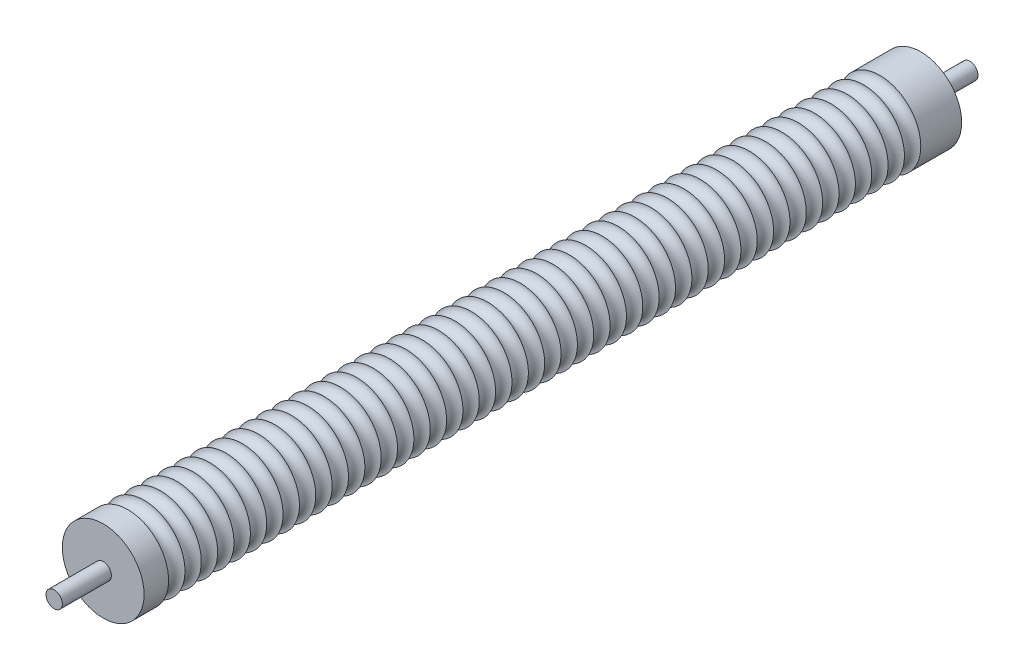
SolidWorks part; units mm, degrees
ref_plane "Front Plane" through (0, 0, 0) normal (0, 0, 1) x (1, 0, 0)
ref_plane "Top Plane" through (0, 0, 0) normal (0, 1, 0) x (1, 0, 0)
ref_plane "Right Plane" through (0, 0, 0) normal (1, 0, 0) x (0, 0, -1)
sketch "Sketch1" plane through (0, 0, 0) normal (0, 0, 1) x (1, 0, 0)
  circle A0 centre (0, 0) radius 50
  dimension "D1" = 100
extrude "Boss-Extrude1" add sketch "Sketch1" along normal blind 1000
sketch "Sketch2" plane through (0, 0, 0) normal (0, 1, 0) x (1, 0, 0)
  line L0 (-50, 0) -> (-50, -1000) construction
  line L1 (-50, -1000) -> (50, -1000) construction
  line L2 (0, 0) -> (0, -1000) construction
  line L3 (-50, -1000) -> (50, -1000) construction
  circle A0 centre (-50, -960) radius 10
  dimension "D1" = 20
  dimension "D2" = 40
revolve "Cut-Revolve1" cut sketch "Sketch2" angle 360 about L2
sketch "Sketch3" plane through (0, 0, 1000) normal (0, 0, 1) x (1, 0, 0)
  circle A1 centre (0, 0) radius 10
  dimension "D1" = 20
extrude "Boss-Extrude2" add sketch "Sketch3" along normal blind 60
ref_plane "Plane1" through (0, 0, 500) normal (0, 0, 1) x (1, 0, 0)
mirror "Mirror1" about plane through (0, 0, 500) normal (0, 0, 1) of "Boss-Extrude2"
sketch "Sketch5" plane through (0, 0, 0) normal (1, 0, 0) x (0, 0, -1)
  line L0 (60, 0) -> (-1060, 0) construction
  line L4 (-1060, 10) -> (-1060, -10) construction
  line L5 (60, -10) -> (60, 10) construction
pattern_linear "LPattern4" count 46 spacing 20 along (0, 0, -1) of "Cut-Revolve1"
